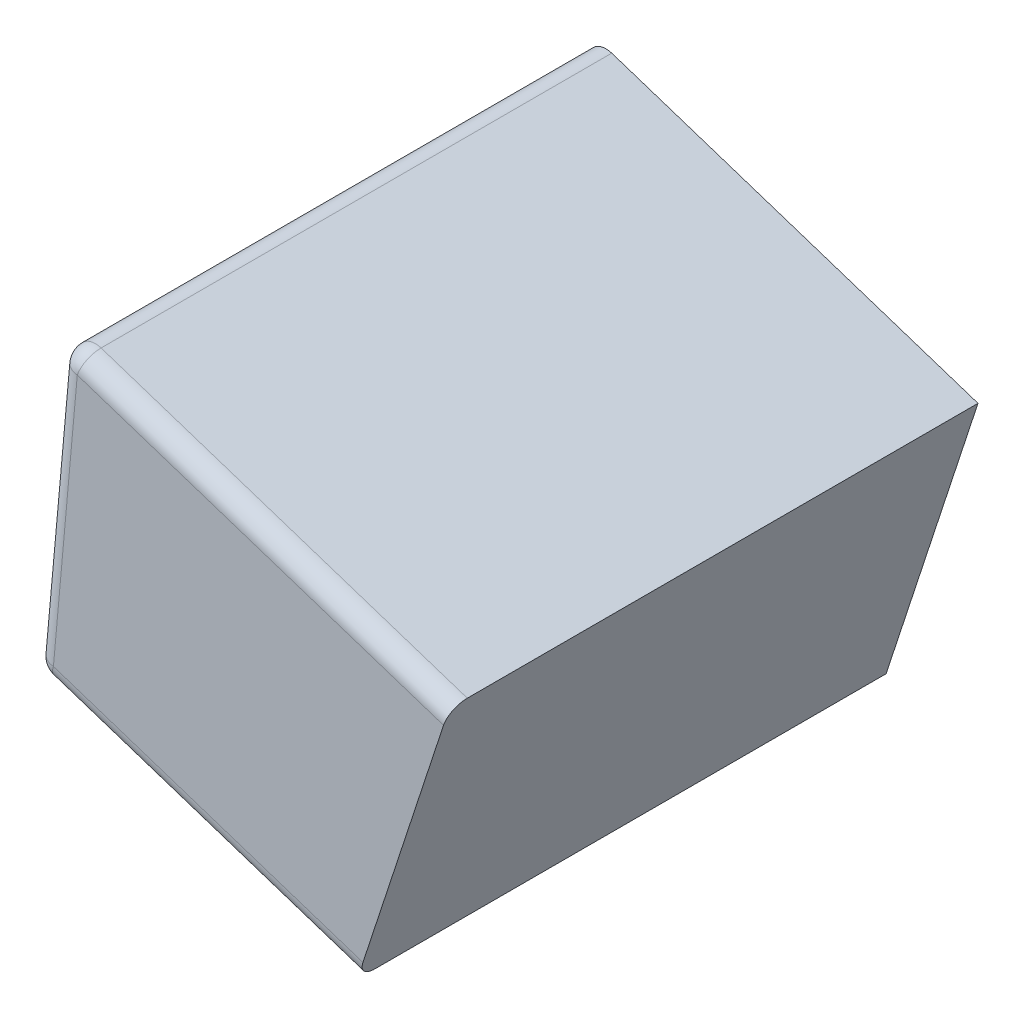
SolidWorks part; units mm, degrees
material "PET"
ref_plane "Front Plane" through (0, 0, 0) normal (0, 0, 1) x (1, 0, 0)
ref_plane "Top Plane" through (0, 0, 0) normal (0, 1, 0) x (1, 0, 0)
ref_plane "Right Plane" through (0, 0, 0) normal (1, 0, 0) x (0, 0, -1)
sketch "Sketch1" plane through (0, 0, 0) normal (0, 0, 1) x (1, 0, 0)
  line L0 (277.6044, 374.8164) -> (281.4152, 417.0054) construction
  line L1 (277.6044, 374.8164) -> (281.4152, 417.0054)
  line L2 (281.4152, 417.0054) -> (335.7181, 399.1921)
  line L3 (335.7181, 399.1921) -> (322.853, 359.9733)
  line L4 (324.8339, 359.3235) -> (277.6044, 374.8164) construction
  line L5 (322.853, 359.9733) -> (277.6044, 374.8164)
  line L6 (247.2747, 82.1423) -> (332.9427, 343.2977) construction
  dimension "D1" = 57.15
extrude "Boss-Extrude1" add sketch "Sketch1" along normal offset from surface (74.025 mm away) 165.1
fillet "Fillet1" radius 2.54 5 edges at (277.6044, 374.8164, 37.0125) (300.2287, 367.3949, 74.025) (279.5098, 395.9109, 74.025) (308.5666, 408.0987, 74.025) (281.4152, 417.0054, 37.0125)
hole_wizard "Hole1" positions "Sketch2" profile "Sketch3" legacy
sketch "Sketch2" plane through (0, 0, 0) normal (0, 0, -1) x (-1, 0, 0)
  line L13 (-332.7492, 390.1416) -> (-280.5358, 407.2694) construction
  line L14 (-322.853, 359.9733) -> (-335.7181, 399.1921) construction
  line L15 (-281.1279, 413.8251) -> (-277.7862, 376.8286) construction
  line L17 (-335.7181, 399.1921) -> (-284.4493, 416.01) construction
  line L18 (-325.8219, 369.0238) -> (-278.4838, 384.5523) construction
  line L20 (-279.5242, 374.1867) -> (-322.853, 359.9733) construction
  line L21 (-323.6987, 393.1105) -> (-316.7714, 371.9927) construction
  line L23 (-289.8243, 404.2225) -> (-287.7724, 381.5053) construction
  point P30 (-323.6987, 393.1105)
  point P32 (-289.8243, 404.2225)
  point P34 (-287.7724, 381.5053)
  point P36 (-316.7714, 371.9927)
  dimension "D1" = 9.525
  dimension "D2" = 9.525
  dimension "D3" = 9.525
  dimension "D4" = 9.525
sketch "Sketch3" plane through (323.6987, 393.1105, 0) normal (1, 0, 0) x (0, 1, 0)
  line L0 (0, 0) -> (0, 4.699)
  line L1 (0, 4.699) -> (2.8702, 4.699)
  line L2 (2.8702, 4.699) -> (2.9972, 0)
  line L3 (2.9972, 0) -> (0, 0)
  line L4 (0, 110) -> (0, -10) construction
  dimension "Minor Diameter" = 5.7404
  dimension "Depth" = 4.699
  dimension "Major Diameter" = 5.9944
hole_wizard "#8 Clearance Hole1" positions "Sketch4" profile "Sketch5" hole size "#8" standard "ANSI Inch"
sketch "Sketch4" plane through (0, 0, 0) normal (0, 0, -1) x (-1, 0, 0)
  point P0 (-323.6987, 393.1105)
  point P3 (-289.8243, 404.2225)
  point P6 (-287.7724, 381.5053)
  point P9 (-316.7714, 371.9927)
sketch "Sketch5" plane through (323.6987, 393.1105, 0) normal (1, 0, 0) x (0, 1, 0)
  line L0 (0, 0) -> (0, 14.1766)
  line L1 (0, 14.1766) -> (2.4574, 12.7)
  line L2 (2.4574, 12.7) -> (2.4574, 0)
  line L5 (2.4574, 0) -> (0, 0)
  line L10 (0, 14.1766) -> (-2.4575, 12.7) construction
  line L11 (0, -6.35) -> (0, 107.95) construction
  dimension "Hole Dia." = 4.9149
  dimension "Hole Depth" = 12.7
  dimension "Drill Angle" = 118
